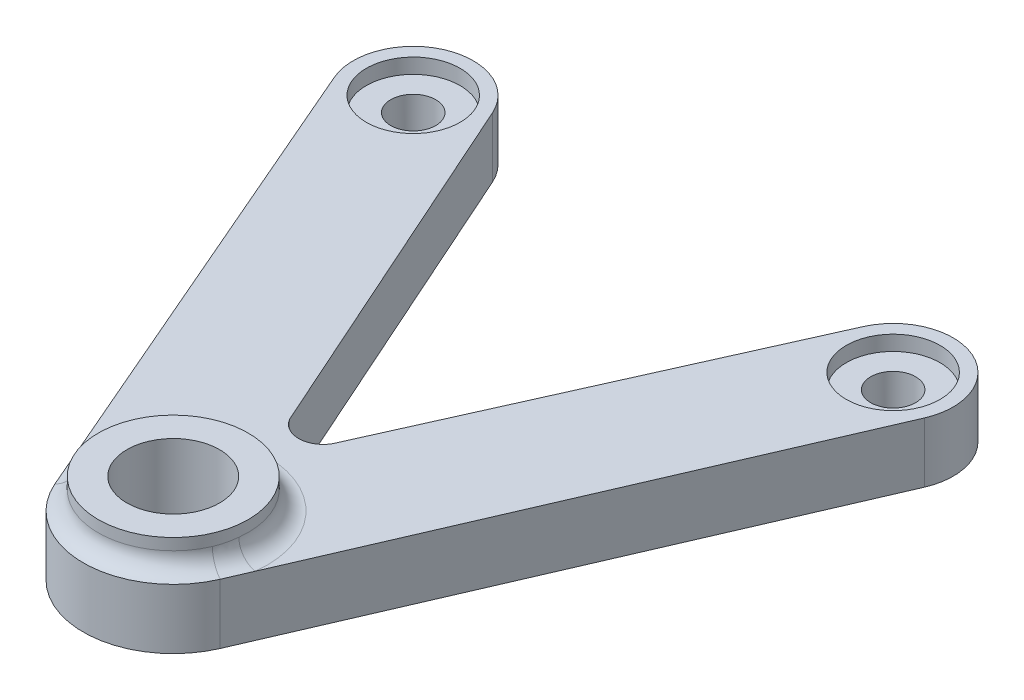
SolidWorks part; units mm, degrees
ref_plane "Front Plane" through (0, 0, 0) normal (0, 0, 1) x (1, 0, 0)
ref_plane "Top Plane" through (0, 0, 0) normal (0, 1, 0) x (1, 0, 0)
ref_plane "Right Plane" through (0, 0, 0) normal (1, 0, 0) x (0, 0, -1)
sketch "Sketch1" plane through (0, 0, 0) normal (0, 1, 0) x (1, 0, 0)
  line L0 (0, 3.2576) -> (0, 54.0576) construction
  line L1 (25.4, 54.0576) -> (-25.4, 54.0576) construction
  line L2 (-2.2602, 17.8405) -> (-19.6025, 56.6484)
  line L3 (2.2602, 17.8405) -> (19.6025, 56.6484)
  line L4 (-1.9098, 19.1326) -> (1.9098, 19.1326) construction
  line L5 (-31.2295, 51.5398) -> (-8.7442, -0.5192)
  line L6 (31.2295, 51.5398) -> (8.7442, -0.5192)
  circle A0 centre (0, 3.2576) radius 4.7625 construction
  circle A1 centre (-25.4, 54.0576) radius 2.3813 construction
  circle A2 centre (25.4, 54.0576) radius 2.3812 construction
  arc A3 (-19.6025, 56.6484) -> (-31.2295, 51.5398) centre (-25.4, 54.0576) ccw
  arc A4 (19.6025, 56.6484) -> (31.2295, 51.5398) centre (25.4, 54.0576) cw
  arc A5 (-8.7442, -0.5192) -> (8.7442, -0.5192) centre (0, 3.2576) ccw
  arc A6 (-2.2602, 17.8405) -> (2.3448, 18.0012) centre (0, 19.1326) ccw
  circle A7 centre (0, 3.2576) radius 7.9375
  point P7 (0, 54.0576)
  point P17 (0, 19.1326)
  dimension "D1" = 50.8
  dimension "D3" = 9.525
  dimension "D4" = 12.7
  dimension "D5" = 15.875
  dimension "D6" = 19.05
  dimension "D2" = 50.8
extrude "Boss-Extrude1" add sketch "Sketch1" along normal blind 6.35 contours A6 L2 A3 L5 A5 L6 A4 L3 region at (0, 0, -15.6084)
hole_wizard "3/16 (0.1875) Diameter Hole1" positions "Sketch3" profile "Sketch2" hole size "3/16" standard "ANSI Inch" end condition through all
sketch "Sketch3" plane through (0, 6.35, 0) normal (0, 1, 0) x (1, 0, 0)
  line L0 (-27.9544, 59.8712) -> (-25.4, 54.0576) construction
  line L1 (27.9544, 59.8712) -> (25.4, 54.0576) construction
  arc A0 (-19.6025, 56.6484) -> (-31.2295, 51.5398) centre (-25.4, 54.0576) ccw construction
  arc A1 (31.2295, 51.5398) -> (19.6025, 56.6484) centre (25.4, 54.0576) ccw construction
  point P3 (-25.4, 54.0576)
  point P13 (25.4, 54.0576)
sketch "Sketch2" plane through (-25.4, 6.35, -54.0576) normal (1, 0, 0) x (0, 0, 1)
  line L0 (0, 0) -> (0, 6.35)
  line L1 (0, 6.35) -> (2.3812, 6.35)
  line L2 (2.3812, 6.35) -> (2.3812, 0)
  line L5 (2.3812, 0) -> (0, 0)
  line L11 (0, -6.35) -> (0, 107.95) construction
  dimension "Thru Hole Dia." = 4.7625
  dimension "Thru Hole Depth" = 6.35
extrude "Boss-Extrude2" add sketch "Sketch1<3>" along normal blind 9.525 contours A7 region at (0, 0, -3.2576)
sketch "Sketch1<3>" plane through (0, 0, 0) normal (0, 1, 0) x (1, 0, 0) same geometry as "Sketch1"
hole_wizard "W (0.386) Diameter Hole1" positions "Sketch8" profile "Sketch7" hole size "W" standard "ANSI Inch" end condition up to next
sketch "Sketch8" plane through (0, 9.525, 0) normal (0, 1, 0) x (1, 0, 0)
  line L0 (0, -4.6799) -> (0, 11.1951) construction
  circle A0 centre (0, 3.2576) radius 7.9375 construction
  point P7 (0, 3.2576)
sketch "Sketch7" plane through (0, 9.525, -3.2576) normal (1, 0, 0) x (0, 0, 1)
  line L0 (0, 0) -> (0, 9.525)
  line L1 (0, 9.525) -> (4.9022, 9.525)
  line L2 (4.9022, 9.525) -> (4.9022, 0)
  line L5 (4.9022, 0) -> (0, 0)
  line L11 (0, -6.35) -> (0, 107.95) construction
  dimension "Thru Hole Dia." = 9.8044
  dimension "Thru Hole Depth" = 9.525
fillet "Fillet1" radius 2 1 edges at (0, 6.35, 4.6799)
hole_wizard "25/64 (0.39063) Diameter Hole1" positions "Sketch10" profile "Sketch11" hole size "25/64" standard "ANSI Inch"
sketch "Sketch10" plane through (0, 6.35, 0) normal (0, 1, 0) x (1, 0, 0)
  point P0 (-25.4, 54.0576)
  point P3 (25.4, 54.0576)
sketch "Sketch11" plane through (-25.4, 6.35, -54.0576) normal (1, 0, 0) x (0, 0, 1)
  line L0 (0, 0) -> (0, 1.5875)
  line L1 (0, 1.5875) -> (4.961, 1.5875)
  line L2 (4.961, 1.5875) -> (4.961, 0)
  line L5 (4.961, 0) -> (0, 0)
  line L10 (0, 1.5875) -> (-4.961, 1.5875) construction
  line L11 (0, -6.35) -> (0, 107.95) construction
  dimension "Hole Dia." = 9.922
  dimension "Hole Depth" = 1.5875
  dimension "Drill Angle" = 180
